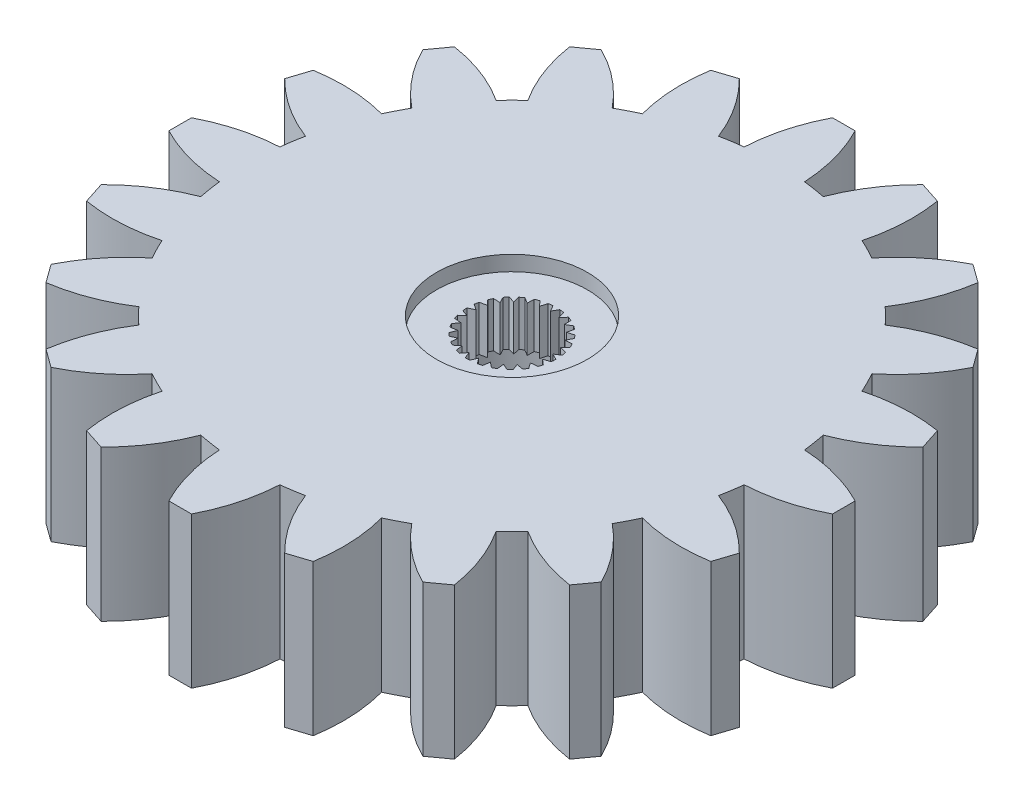
SolidWorks part; units mm, degrees
ref_plane "Front Plane" through (0, 0, 0) normal (0, 0, 1) x (1, 0, 0)
ref_plane "Top Plane" through (0, 0, 0) normal (0, 1, 0) x (1, 0, 0)
ref_plane "Right Plane" through (0, 0, 0) normal (1, 0, 0) x (0, 0, -1)
sketch "Sketch2" plane through (0, 0, 0) normal (0, 1, 0) x (1, 0, 0)
  line L0 (0, -10.2886) -> (0, 10.2886) construction
  line L1 (0, 0) -> (0.6267, 4.1579) construction
  line L2 (0, 0) -> (-0.6267, 4.1579) construction
  line L3 (0, 0) -> (1.373, 17.4461) construction
  line L4 (0, 0) -> (-1.373, 17.4461) construction
  line L5 (-0.2259, 2.9413) -> (0, 2.55)
  line L6 (0, 2.55) -> (0.2259, 2.9413)
  line L7 (-0.75, 21.9872) -> (0.75, 21.9872)
  line L8 (0.6342, 2.4699) -> (0.9503, 2.7927)
  line L9 (7.8676, 46.3212) -> (7.9539, 46.8293)
  line L10 (3.8992, 46.8226) -> (3.9419, 47.3362)
  line L11 (0.5126, 2.9051) -> (0.6342, 2.4699)
  line L12 (13.6112, 44.9699) -> (13.7605, 45.4632)
  line L13 (9.7368, 45.9647) -> (9.8436, 46.4688)
  line L14 (1.2285, 2.2346) -> (1.615, 2.4687)
  line L15 (19.1401, 42.9094) -> (19.35, 43.38)
  line L16 (15.421, 44.3819) -> (15.5901, 44.8687)
  line L17 (1.219, 2.6864) -> (1.2285, 2.2346)
  line L18 (24.3671, 40.1721) -> (24.6344, 40.6128)
  line L19 (20.8619, 42.0991) -> (21.0907, 42.5609)
  line L20 (1.7456, 1.8589) -> (2.1782, 1.9895)
  line L21 (29.2099, 36.8013) -> (29.5303, 37.205)
  line L22 (25.9738, 39.1525) -> (26.2587, 39.5819)
  line L23 (1.8488, 2.2988) -> (1.7456, 1.8589)
  line L24 (33.592, 32.8502) -> (33.9604, 33.2105)
  line L25 (30.6761, 35.5884) -> (31.0126, 35.9787)
  line L26 (2.153, 1.3664) -> (2.6045, 1.3853)
  line L27 (37.4443, 28.381) -> (37.855, 28.6923)
  line L28 (34.8946, 31.463) -> (35.2774, 31.8081)
  line L29 (2.3624, 1.7668) -> (2.153, 1.3664)
  line L30 (40.7061, 23.4641) -> (41.1526, 23.7215)
  line L31 (38.5628, 26.8415) -> (38.9858, 27.1359)
  line L32 (2.4252, 0.788) -> (2.8672, 0.694)
  line L33 (43.326, 18.1773) -> (43.8012, 18.3767)
  line L34 (41.6229, 21.7966) -> (42.0794, 22.0357)
  line L35 (2.7276, 1.1238) -> (2.4252, 0.788)
  line L36 (45.2626, 12.6038) -> (45.7591, 12.742)
  line L37 (44.0265, 16.408) -> (44.5094, 16.588)
  line L38 (2.545, 0.1601) -> (2.9497, -0.0408)
  line L39 (46.4853, 6.8315) -> (46.9952, 6.9064)
  line L40 (45.7358, 10.7606) -> (46.2375, 10.8787)
  line L41 (2.9213, 0.4102) -> (2.545, 0.1601)
  line L42 (46.975, 0.9515) -> (47.4903, 0.9619)
  line L43 (46.7238, 4.9436) -> (47.2363, 4.9978)
  line L44 (2.5048, -0.4778) -> (2.8469, -0.7731)
  line L45 (46.7238, -4.9436) -> (47.2363, -4.9978)
  line L46 (46.975, -0.9515) -> (47.4903, -0.9619)
  line L47 (2.9316, -0.3292) -> (2.5048, -0.4778)
  line L48 (45.7358, -10.7606) -> (46.2375, -10.8787)
  line L49 (46.4853, -6.8315) -> (46.9952, -6.9064)
  line L50 (2.3073, -1.0857) -> (2.5652, -1.4568)
  line L51 (44.0265, -16.408) -> (44.5094, -16.588)
  line L52 (45.2626, -12.6038) -> (45.7591, -12.742)
  line L53 (2.7576, -1.0479) -> (2.3073, -1.0857)
  line L54 (41.6229, -21.7966) -> (42.0794, -22.0357)
  line L55 (43.326, -18.1773) -> (43.8012, -18.3767)
  line L56 (1.9648, -1.6254) -> (2.1223, -2.049)
  line L57 (38.5628, -26.8415) -> (38.9858, -27.1359)
  line L58 (40.7061, -23.4641) -> (41.1526, -23.7215)
  line L59 (2.4104, -1.7008) -> (1.9648, -1.6254)
  line L60 (34.8946, -31.463) -> (35.2774, -31.8081)
  line L61 (37.4443, -28.381) -> (37.855, -28.6923)
  line L62 (1.4989, -2.063) -> (1.5461, -2.5124)
  line L63 (30.6761, -35.5884) -> (31.0126, -35.9787)
  line L64 (33.592, -32.8502) -> (33.9604, -33.2105)
  line L65 (1.9117, -2.2468) -> (1.4989, -2.063)
  line L66 (25.9738, -39.1525) -> (26.2587, -39.5819)
  line L67 (29.2099, -36.8013) -> (29.5303, -37.205)
  line L68 (0.9387, -2.3709) -> (0.8727, -2.818)
  line L69 (20.8619, -42.0991) -> (21.0907, -42.5609)
  line L70 (24.3671, -40.1721) -> (24.6344, -40.6128)
  line L71 (1.2928, -2.6516) -> (0.9387, -2.3709)
  line L72 (15.421, -44.3819) -> (15.5901, -44.8687)
  line L73 (19.1401, -42.9094) -> (19.35, -43.38)
  line L74 (0.3196, -2.5299) -> (0.1445, -2.9465)
  line L75 (9.7368, -45.9647) -> (9.8436, -46.4688)
  line L76 (13.6112, -44.9699) -> (13.7605, -45.4632)
  line L77 (0.5928, -2.8898) -> (0.3196, -2.5299)
  line L78 (3.8992, -46.8226) -> (3.9419, -47.3362)
  line L79 (7.8676, -46.3212) -> (7.9539, -46.8293)
  line L80 (-0.3196, -2.5299) -> (-0.5928, -2.8898)
  line L81 (-2, -46.942) -> (-2.0219, -47.4569)
  line L82 (2, -46.942) -> (2.0219, -47.4569)
  line L83 (-0.1445, -2.9465) -> (-0.3196, -2.5299)
  line L84 (-7.8676, -46.3212) -> (-7.9539, -46.8293)
  line L85 (-3.8992, -46.8226) -> (-3.9419, -47.3362)
  line L86 (-0.9387, -2.3709) -> (-1.2928, -2.6516)
  line L87 (-13.6112, -44.9699) -> (-13.7605, -45.4632)
  line L88 (-9.7368, -45.9647) -> (-9.8436, -46.4688)
  line L89 (-0.8727, -2.818) -> (-0.9387, -2.3709)
  line L90 (-19.1401, -42.9094) -> (-19.35, -43.38)
  line L91 (-15.421, -44.3819) -> (-15.5901, -44.8687)
  line L92 (-1.4989, -2.063) -> (-1.9117, -2.2468)
  line L93 (-24.3671, -40.1721) -> (-24.6344, -40.6128)
  line L94 (-20.8619, -42.0991) -> (-21.0907, -42.5609)
  line L95 (-1.5461, -2.5124) -> (-1.4989, -2.063)
  line L96 (-29.2099, -36.8013) -> (-29.5303, -37.205)
  line L97 (-25.9738, -39.1525) -> (-26.2587, -39.5819)
  line L98 (-1.9648, -1.6254) -> (-2.4104, -1.7008)
  line L99 (-33.592, -32.8502) -> (-33.9604, -33.2105)
  line L100 (-30.6761, -35.5884) -> (-31.0126, -35.9787)
  line L101 (-2.1223, -2.049) -> (-1.9648, -1.6254)
  line L102 (-37.4443, -28.381) -> (-37.855, -28.6923)
  line L103 (-34.8946, -31.463) -> (-35.2774, -31.8081)
  line L104 (-2.3073, -1.0857) -> (-2.7576, -1.0479)
  line L105 (-40.7061, -23.4641) -> (-41.1526, -23.7215)
  line L106 (-38.5628, -26.8415) -> (-38.9858, -27.1359)
  line L107 (-2.5652, -1.4568) -> (-2.3073, -1.0857)
  line L108 (-43.326, -18.1773) -> (-43.8012, -18.3767)
  line L109 (-41.6229, -21.7966) -> (-42.0794, -22.0357)
  line L110 (-2.5048, -0.4778) -> (-2.9316, -0.3292)
  line L111 (-45.2626, -12.6038) -> (-45.7591, -12.742)
  line L112 (-44.0265, -16.408) -> (-44.5094, -16.588)
  line L113 (-2.8469, -0.7731) -> (-2.5048, -0.4778)
  line L114 (-46.4853, -6.8315) -> (-46.9952, -6.9064)
  line L115 (-45.7358, -10.7606) -> (-46.2375, -10.8787)
  line L116 (-2.545, 0.1601) -> (-2.9213, 0.4102)
  line L117 (-46.975, -0.9515) -> (-47.4903, -0.9619)
  line L118 (-46.7238, -4.9436) -> (-47.2363, -4.9978)
  line L119 (-2.9497, -0.0408) -> (-2.545, 0.1601)
  line L120 (-46.7238, 4.9436) -> (-47.2363, 4.9978)
  line L121 (-46.975, 0.9515) -> (-47.4903, 0.9619)
  line L122 (-2.4252, 0.788) -> (-2.7276, 1.1238)
  line L123 (-45.7358, 10.7606) -> (-46.2375, 10.8787)
  line L124 (-46.4853, 6.8315) -> (-46.9952, 6.9064)
  line L125 (-2.8672, 0.694) -> (-2.4252, 0.788)
  line L126 (-44.0265, 16.408) -> (-44.5094, 16.588)
  line L127 (-45.2626, 12.6038) -> (-45.7591, 12.742)
  line L128 (-2.153, 1.3664) -> (-2.3624, 1.7668)
  line L129 (-41.6229, 21.7966) -> (-42.0794, 22.0357)
  line L130 (-43.326, 18.1773) -> (-43.8012, 18.3767)
  line L131 (-2.6045, 1.3853) -> (-2.153, 1.3664)
  line L132 (-38.5628, 26.8415) -> (-38.9858, 27.1359)
  line L133 (-40.7061, 23.4641) -> (-41.1526, 23.7215)
  line L134 (-1.7456, 1.8589) -> (-1.8488, 2.2988)
  line L135 (-34.8946, 31.463) -> (-35.2774, 31.8081)
  line L136 (-37.4443, 28.381) -> (-37.855, 28.6923)
  line L137 (-2.1782, 1.9895) -> (-1.7456, 1.8589)
  line L138 (-30.6761, 35.5884) -> (-31.0126, 35.9787)
  line L139 (-33.592, 32.8502) -> (-33.9604, 33.2105)
  line L140 (-1.2285, 2.2346) -> (-1.219, 2.6864)
  line L141 (-25.9738, 39.1525) -> (-26.2587, 39.5819)
  line L142 (-29.2099, 36.8013) -> (-29.5303, 37.205)
  line L143 (-1.615, 2.4687) -> (-1.2285, 2.2346)
  line L144 (-20.8619, 42.0991) -> (-21.0907, 42.5609)
  line L145 (-24.3671, 40.1721) -> (-24.6344, 40.6128)
  line L146 (-0.6342, 2.4699) -> (-0.5126, 2.9051)
  line L147 (-15.421, 44.3819) -> (-15.5901, 44.8687)
  line L148 (-19.1401, 42.9094) -> (-19.35, 43.38)
  line L149 (-0.9503, 2.7927) -> (-0.6342, 2.4699)
  line L150 (-9.7368, 45.9647) -> (-9.8436, 46.4688)
  line L151 (-13.6112, 44.9699) -> (-13.7605, 45.4632)
  line L153 (-3.8992, 46.8226) -> (-3.9419, 47.3362)
  line L154 (-7.8676, 46.3212) -> (-7.9539, 46.8293)
  circle A0 centre (0, 0) radius 18.7939 construction
  circle A1 centre (0, 0) radius 2.55 construction
  circle A2 centre (0, 0) radius 2.95
  circle A24 centre (0, 0) radius 17.5
  circle A25 centre (0, 0) radius 20 construction
  circle A26 centre (0, 0) radius 22 construction
  arc A27 (0.75, 21.9872) -> (2, 17.3853) centre (-9.2545, 16.799) cw
  arc A28 (-0.75, 21.9872) -> (-2, 17.3853) centre (9.2545, 16.799) ccw
  point P7 (0, 0)
  point P30 (1.5692, 19.9383)
  point P78 (0, 0)
  point P139 (0, 0)
  point P226 (0, 0)
  dimension "D1" = 5.1
  dimension "D3" = 5.9
  dimension "D5" = 37.5877
  dimension "D6" = 35
  dimension "D7" = 40
  dimension "D8" = 44
  dimension "D2" = 8.571
  dimension "D9" = 4.5
  dimension "D11" = 1.5
  dimension "D12" = 4
  dimension "D4" = 60
  dimension "D10" = 30
  dimension "D13" = 25
extrude "Boss-Extrude1" add sketch "Sketch2" along normal blind 10 contours A24 | A2 region at (0, 0, -17.005)
extrude "Boss-Extrude2" add sketch "Sketch2<4>" along normal up to surface (10 mm away) contours L7 A28 A24 A27 region at (0, 0, -19.4231) up to face at (0, 10, 17.5)
sketch "Sketch2<4>" plane through (0, 0, 0) normal (0, 1, 0) x (1, 0, 0) same geometry as "Sketch2"
pattern_circular "CirPattern1" count 20 over 360 about axis through (0, 10, 0) along (0, 1, 0) of "Boss-Extrude2"
extrude "Cut-Extrude2" cut sketch "Sketch2<7>" against normal blind 4 from surface contours L77 A2 L68 L71 L62 L65 L56 L59 L50 L53 L44 L47 L38 L41 L32 L35 L26 L29 L20 L23 L14 L17 L8 L11 L6 L5 L146 L149 L140 L143 L134 L137 L128 L131 L122 region at (0, 0, 0) starting at face at (0, 10, 0)
sketch "Sketch2<7>" plane through (0, 0, 0) normal (0, 1, 0) x (1, 0, 0) same geometry as "Sketch2"
sketch "Sketch3" plane through (0, 0, 0) normal (0, -1, 0) x (1, 0, 0)
  circle A0 centre (0, 0) radius 5
  dimension "D1" = 10
extrude "Cut-Extrude3" cut sketch "Sketch3" against normal up to surface (6 mm away) up to face at (0, 6, 0)
sketch "Sketch4" plane through (0, 10, 0) normal (0, 1, 0) x (1, 0, 0)
  circle A0 centre (0, 0) radius 5
  dimension "D1" = 10
extrude "Cut-Extrude4" cut sketch "Sketch4" against normal blind 1
equation "\"Module\"= 2"
equation "\"Teeth\"= 20"
equation "\"Pitch Diameter\"= \"Module\" * \"Teeth\""
equation "\"Outer Diamter\"= \"Pitch Diameter\" + ( 2 * \"Module\" )"
equation "\"Root Diameter\"= \"Pitch Diameter\" - ( 2.5 * \"Module\" )"
equation "\"Base Diamter\"= \"Pitch Diameter\" * cos ( 20 )"
equation "\"D5@Sketch2\"=\"Base Diamter\""
equation "\"D6@Sketch2\"=\"Root Diameter\""
equation "\"D8@Sketch2\"=\"Outer Diamter\""
equation "\"D9@Sketch2\"=90 / \"Teeth\""
equation "\"D7@Sketch2\"=\"Pitch Diameter\""
equation "\"D1@CirPattern1\"=\"Teeth\""
